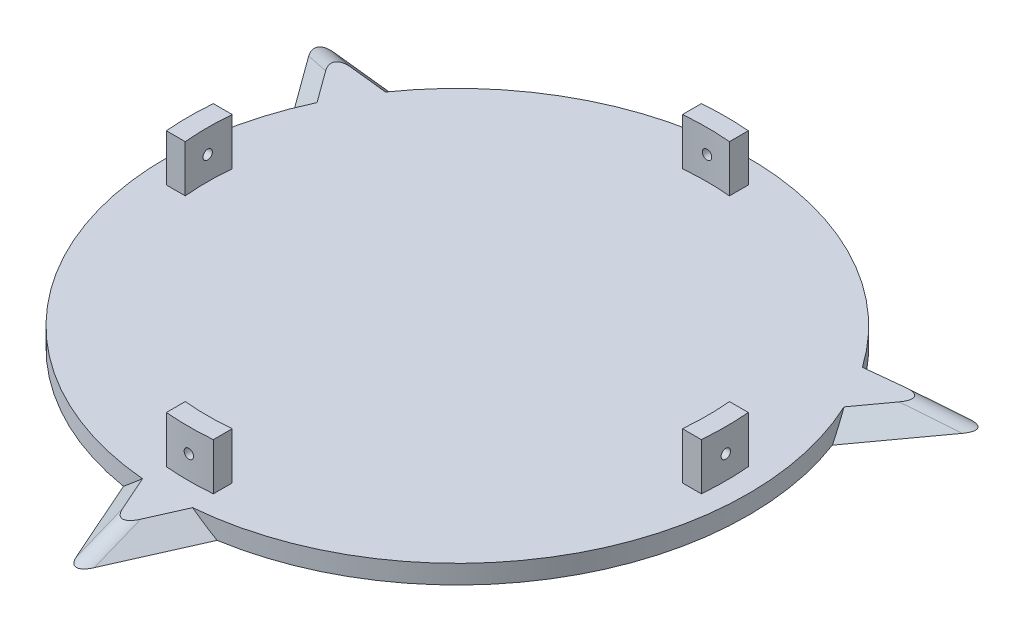
SolidWorks part; units mm, degrees
ref_plane "Front Plane" through (0, 0, 0) normal (0, 0, 1) x (1, 0, 0)
ref_plane "Top Plane" through (0, 0, 0) normal (0, 1, 0) x (1, 0, 0)
ref_plane "Right Plane" through (0, 0, 0) normal (1, 0, 0) x (0, 0, -1)
sketch "Sketch4" plane through (0, 0, 0) normal (0, 1, 0) x (1, 0, 0)
  circle A0 centre (0, 0) radius 61.9125
extrude "Boss-Extrude1" add sketch "Sketch4" against normal blind 4 contours A0
sketch "Sketch15" plane through (0, 0, 0) normal (0, 1, 0) x (1, 0, 0)
  line L0 (-52.9143, -5) -> (-56.9309, -5)
  line L1 (-52.9143, 5) -> (-56.9309, 5)
  line L2 (-5, 52.9143) -> (-5, 56.9309)
  line L3 (-5, -52.9143) -> (-5, -56.9309)
  line L4 (5, -52.9143) -> (5, -56.9309)
  line L5 (5, 52.9143) -> (5, 56.9309)
  line L6 (52.9143, 5) -> (56.9309, 5)
  line L7 (52.9143, -5) -> (56.9309, -5)
  arc A0 (-5, -56.9309) -> (5, -56.9309) centre (0, 0) ccw
  arc A1 (-5, -52.9143) -> (5, -52.9143) centre (0, 0) ccw
  arc A2 (-56.9309, 5) -> (-56.9309, -5) centre (0, 0) ccw
  arc A3 (-52.9143, 5) -> (-52.9143, -5) centre (0, 0) ccw
  arc A4 (5, 56.9309) -> (-5, 56.9309) centre (0, 0) ccw
  arc A5 (5, 52.9143) -> (-5, 52.9143) centre (0, 0) ccw
  arc A6 (56.9309, -5) -> (56.9309, 5) centre (0, 0) ccw
  arc A7 (52.9143, -5) -> (52.9143, 5) centre (0, 0) ccw
  point P21 (0, 0)
  dimension "D1" = 4
extrude "Boss-Extrude2" add sketch "Sketch15" along normal blind 10 contours L0 A2 L1 A3 | L2 A4 L5 A5 | L6 A6 L7 A7 | A0 L4 A1 L3
sketch3d "3DSketch1"
  line L0 (0, 10, 57.15) -> (0, 0, 57.15)
  arc A0 (-5, 10, 56.9309) -> (5, 10, 56.9309) centre (0, 10, 0) ccw construction
  arc A1 (-5, 0, 56.9309) -> (5, 0, 56.9309) centre (0, 0, 0) ccw construction
  point P5 (0, 67.15, 0)
  point P9 (0, 57.15, 0)
hole_wizard "M2 Clearance Hole2" positions "3DSketch3" profile "Sketch17" hole size "M2" standard "ANSI Metric" end condition through all
sketch3d "3DSketch3"
  point P0 (0, 5, 57.15)
  point P2 (0, 5, 57.15)
  point P4 (0, 5, 57.15)
  point P6 (0, 5, 57.15)
  point P8 (0, 5, 57.15)
  point P10 (0, 5, 57.15)
  point P12 (0, 5, 57.15)
  point P14 (0, 5, 57.15)
  point P16 (0, 5, 57.15)
  point P18 (0, 5, 57.15)
  point P20 (0, 5, 57.15)
sketch "Sketch17" plane through (0, 5, 57.15) normal (1, 0, 0) x (0, -1, 0)
  line L0 (0, 0) -> (0, 119.0625)
  line L1 (0, 119.0625) -> (1, 119.0625)
  line L2 (1, 119.0625) -> (1, 0)
  line L5 (1, 0) -> (0, 0)
  line L11 (0, -6.35) -> (0, 107.95) construction
  dimension "Thru Hole Dia." = 2
  dimension "Thru Hole Depth" = 119.0625
sketch3d "3DSketch4"
  line L0 (57.15, 10, 0) -> (57.15, 0, 0)
  arc A0 (56.9309, 10, 5) -> (56.9309, 10, -5) centre (0, 10, 0) ccw construction
  arc A1 (56.9309, 0, 5) -> (56.9309, 0, -5) centre (0, 0, 0) ccw construction
  point P5 (0, 67.15, 0)
  point P9 (0, 57.15, 0)
hole_wizard "M2 Clearance Hole3" positions "3DSketch5" profile "Sketch18" hole size "M2" standard "ANSI Metric" end condition through all
sketch3d "3DSketch5"
  point P0 (57.15, 5, 0)
sketch "Sketch18" plane through (57.15, 5, 0) normal (0, 1, 0) x (0, 0, -1)
  line L0 (0, 0) -> (0, 119.0625)
  line L1 (0, 119.0625) -> (1, 119.0625)
  line L2 (1, 119.0625) -> (1, 0)
  line L5 (1, 0) -> (0, 0)
  line L11 (0, -6.35) -> (0, 107.95) construction
  dimension "Thru Hole Dia." = 2
  dimension "Thru Hole Depth" = 119.0625
sketch "Sketch19" plane through (0, 0, 0) normal (0, 1, 0) x (1, 0, 0)
  line L2 (9.9673, -61.1049) -> (0, -83.5648)
  line L3 (-47.9347, 39.1844) -> (-72.3693, 41.7824)
  line L4 (-9.9673, -61.1049) -> (0, -83.5648)
  line L5 (-57.9021, 21.9205) -> (-72.3693, 41.7824)
  line L6 (57.9021, 21.9205) -> (72.3693, 41.7824)
  line L7 (47.9347, 39.1844) -> (72.3693, 41.7824)
  arc A0 (-9.9673, -61.1049) -> (9.9673, -61.1049) centre (0, 0) ccw
  arc A2 (-47.9347, 39.1844) -> (-57.9021, 21.9205) centre (0, 0) ccw
  arc A3 (57.9021, 21.9205) -> (47.9347, 39.1844) centre (0, 0) ccw
  point P13 (0, 0)
  dimension "D1" = 3
extrude "Boss-Extrude3" add sketch "Sketch19" against normal blind 4
chamfer "Chamfer1" distance 4 angle 45 6 edges at (-60.152, 0, -40.4834) (-65.1357, 0, -31.8515) (60.152, 0, -40.4834) (65.1357, 0, -31.8515) (4.9837, 0, 72.3349) (-4.9837, 0, 72.3349)
fillet "Fillet1" radius 3 3 edges at (68.0993, -2, -39.3171) (-68.0993, -2, -39.3171) (0, -2, 78.6343)
